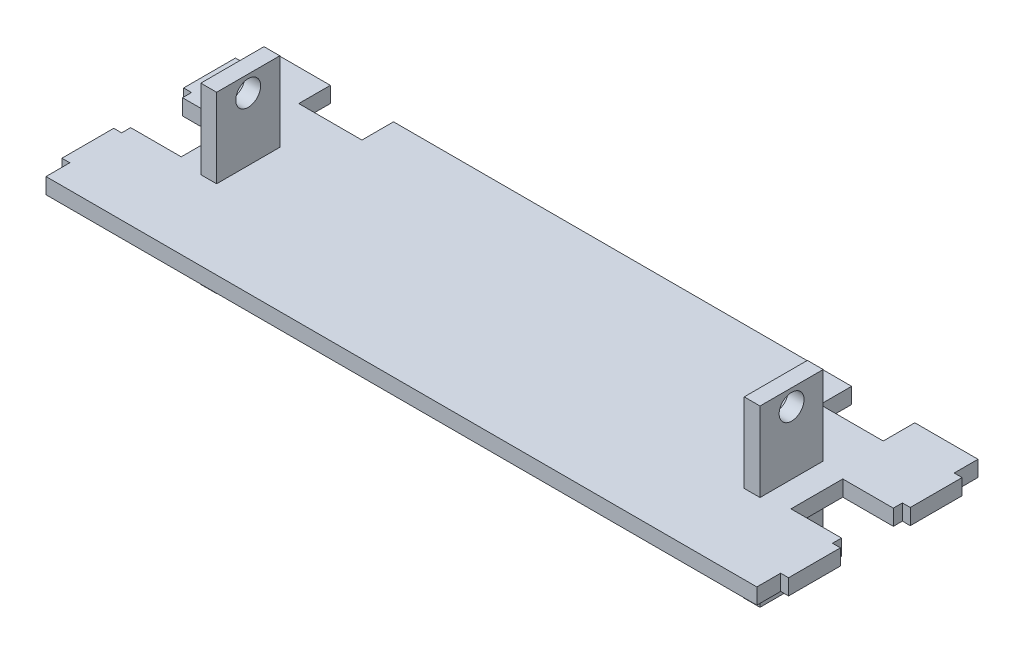
SolidWorks part; units mm, degrees
ref_plane "Front Plane" through (0, 0, 0) normal (0, 0, 1) x (1, 0, 0)
ref_plane "Top Plane" through (0, 0, 0) normal (0, 1, 0) x (1, 0, 0)
ref_plane "Right Plane" through (0, 0, 0) normal (1, 0, 0) x (0, 0, -1)
sketch "Sketch1" plane through (0, 0, 0) normal (0, 1, 0) x (1, 0, 0)
  line L0 (0, 72.39) -> (0, -44.45) construction
  line L1 (142.875, -44.45) -> (-142.875, -44.45)
  line L2 (142.875, -44.45) -> (142.875, -34.8747)
  line L3 (142.875, 44.45) -> (117.475, 44.45)
  line L4 (-142.875, -44.45) -> (-142.875, -34.8747)
  line L5 (142.875, -44.45) -> (-142.875, 44.45) construction
  line L6 (142.875, 44.45) -> (-142.875, -44.45) construction
  line L7 (142.875, 10.414) -> (122.555, 10.414)
  line L9 (142.875, -10.414) -> (122.555, -10.414)
  line L10 (122.555, 10.414) -> (122.555, -10.414)
  line L11 (-117.475, 44.45) -> (-142.875, 44.45)
  line L13 (-142.875, -10.414) -> (-122.555, -10.414)
  line L14 (-122.555, 10.414) -> (-122.555, -10.414)
  line L15 (-142.875, 10.414) -> (-122.555, 10.414)
  line L17 (-127, 0) -> (127, 0) construction
  line L18 (-142.875, 14.0467) -> (-146.05, 14.0467)
  line L20 (-142.875, 34.8747) -> (-146.05, 34.8747)
  line L21 (-146.05, 14.0467) -> (-146.05, 34.8747)
  line L22 (-142.875, -34.8747) -> (-146.05, -34.8747)
  line L23 (-146.05, -14.0467) -> (-146.05, -34.8747)
  line L24 (-142.875, -14.0467) -> (-146.05, -14.0467)
  line L27 (142.875, -14.0467) -> (146.05, -14.0467)
  line L28 (146.05, -14.0467) -> (146.05, -34.8747)
  line L29 (142.875, -34.8747) -> (146.05, -34.8747)
  line L30 (142.875, 34.8747) -> (146.05, 34.8747)
  line L31 (146.05, 14.0467) -> (146.05, 34.8747)
  line L32 (142.875, 14.0467) -> (146.05, 14.0467)
  line L34 (-142.875, 34.8747) -> (-142.875, 44.45)
  line L35 (-142.875, -14.0467) -> (-142.875, -10.414)
  line L36 (142.875, 34.8747) -> (142.875, 44.45)
  line L37 (142.875, -14.0467) -> (142.875, -10.414)
  line L38 (-142.875, 10.414) -> (-142.875, 14.0467)
  line L39 (142.875, 10.414) -> (142.875, 14.0467)
  line L40 (-117.475, 44.45) -> (-117.475, 31.75)
  line L41 (-117.475, 31.75) -> (-92.075, 31.75)
  line L42 (-92.075, 44.45) -> (-92.075, 31.75)
  line L44 (92.075, 44.45) -> (92.075, 31.75)
  line L45 (92.075, 31.75) -> (117.475, 31.75)
  line L46 (117.475, 44.45) -> (117.475, 31.75)
  line L47 (92.075, 44.45) -> (-92.075, 44.45)
  point P0 (0, 0)
  point P6 (127, 0)
  dimension "D1" = 285.75
  dimension "D2" = 88.9
  dimension "D3" = 20.828
  dimension "D5" = 3.175
  dimension "D6" = 20.828
  dimension "D4" = 20.32
  dimension "D7" = 12.7
  dimension "D8" = 25.4
  dimension "D9" = 25.4
  dimension "D10" = 12.7
  dimension "D12" = 25.4
  dimension "D11" = 25.4
extrude "Boss-Extrude1" add sketch "Sketch1" along normal mid plane 6.35
sketch "Sketch2" plane through (0, 0, 0) normal (0, 1, 0) x (1, 0, 0)
  line L1 (106.045, -12.7) -> (112.395, -12.7)
  line L2 (106.045, -12.7) -> (106.045, 12.7)
  line L3 (106.045, 12.7) -> (112.395, 12.7)
  line L4 (112.395, -12.7) -> (112.395, 12.7)
  line L5 (106.045, -12.7) -> (112.395, 12.7) construction
  line L6 (106.045, 12.7) -> (112.395, -12.7) construction
  line L7 (0, 44.45) -> (0, -44.45) construction
  line L8 (92.075, 44.45) -> (-92.075, 44.45) construction
  line L13 (122.555, -10.414) -> (122.555, 10.414) construction
  line L14 (-142.875, -44.45) -> (142.875, -44.45) construction
  line L15 (-106.045, -12.7) -> (-106.045, 12.7)
  line L16 (-106.045, -12.7) -> (-112.395, -12.7)
  line L17 (-112.395, -12.7) -> (-112.395, 12.7)
  line L18 (-106.045, 12.7) -> (-112.395, 12.7)
  point P0 (109.22, 0)
  point P10 (122.555, 0)
  dimension "D2" = 10.16
  dimension "D4" = 25.4
  dimension "D5" = 6.35
extrude "Boss-Extrude2" add sketch "Sketch2" along normal mid plane 70.104
sketch "Sketch5" plane through (-112.395, 0, 0) normal (-1, 0, 0) x (0, 0, 1)
  line L1 (-44.45, 0) -> (44.45, 0) construction
  line L2 (-44.45, 3.175) -> (-44.45, -3.175) construction
  line L3 (44.45, 3.175) -> (44.45, -3.175) construction
  circle A0 centre (0, 28.448) radius 5.0038
  circle A1 centre (0, -28.448) radius 5.0038
  dimension "D2" = 10.0076
extrude "Cut-Extrude1" cut sketch "Sketch5" against normal through all both and the other way through all
equation "\"length\"=11.25"
equation "\"width\"=3.5"
equation "\"height\"= 0.25"
equation "\"D1@Sketch1\"=\"length\""
equation "\"D2@Sketch1\"=\"width\""
equation "\"eyebolt width\"= 0.82"
equation "\"eyebolt length\"= 0.8"
equation "\"D3@Sketch1\"=\"eyebolt width\""
equation "\"D4@Sketch1\"=\"eyebolt length\""
equation "\"lead screw holder height\"= 2.76"
equation "\"lead screw diameter\"=0.394"
equation "\"distance from holders to board\"=0.4"
equation "\"D2@Sketch5\"=\"lead screw diameter\""
